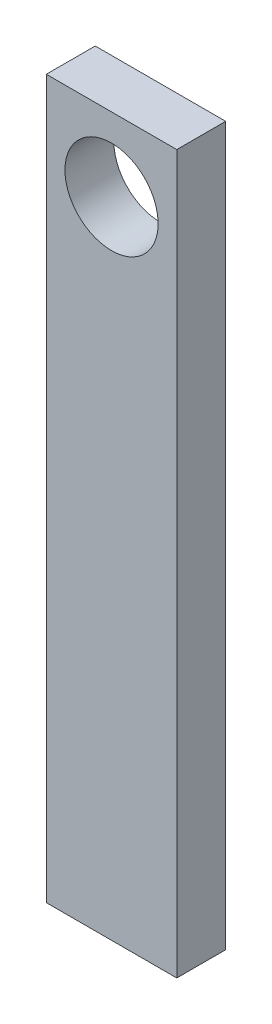
SolidWorks part; units mm, degrees
ref_plane "Front Plane" through (0, 0, 0) normal (0, 0, 1) x (1, 0, 0)
ref_plane "Top Plane" through (0, 0, 0) normal (0, 1, 0) x (1, 0, 0)
ref_plane "Right Plane" through (0, 0, 0) normal (1, 0, 0) x (0, 0, -1)
sketch "Sketch1" plane through (0, 0, 0) normal (-1, 0, 0) x (0, 0, 1)
  line L1 (-15, 190) -> (0, 190)
  line L2 (-15, 190) -> (-15, -30)
  line L3 (-15, -30) -> (0, -30)
  line L4 (0, 190) -> (0, -30)
  dimension "D1" = 30
  dimension "D2" = 220
  dimension "D3" = 15
extrude "Boss-Extrude1" add sketch "Sketch1" along normal blind 20 and the other way blind 20
sketch "Sketch5" plane through (0, 0, -15) normal (0, 0, -1) x (-1, 0, 0)
  circle A0 centre (0, 167.4436) radius 14.2875
extrude "Cut-Extrude1" cut sketch "Sketch5" against normal up to next
